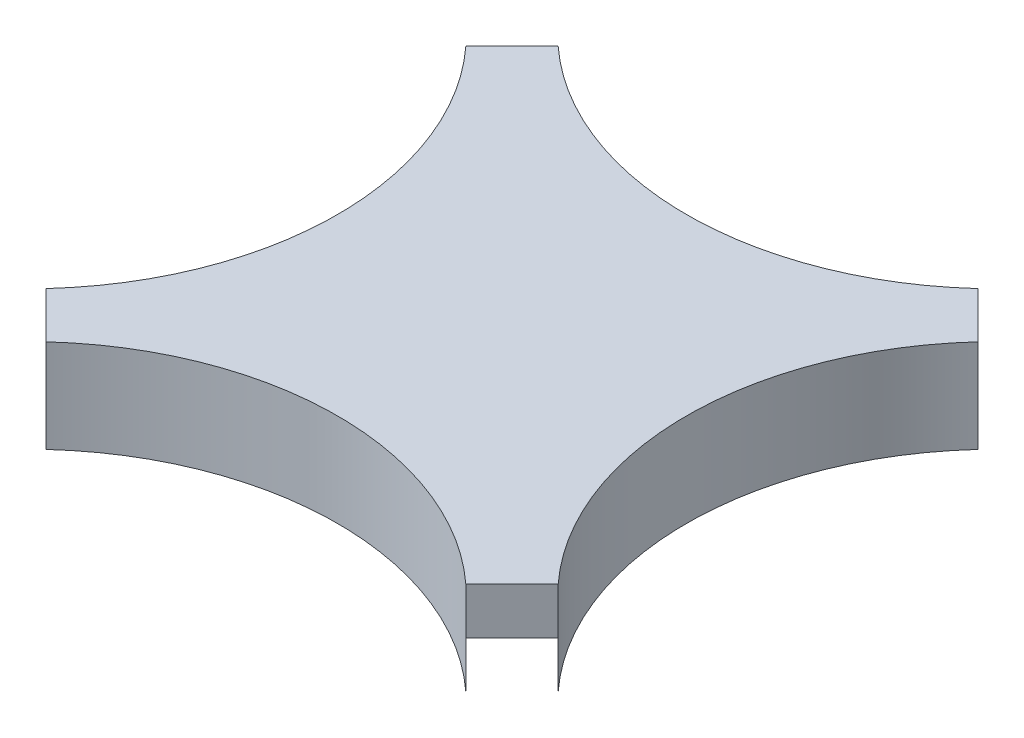
SolidWorks part; units mm, degrees
ref_plane "Front Plane" through (0, 0, 0) normal (0, 0, 1) x (1, 0, 0)
ref_plane "Top Plane" through (0, 0, 0) normal (0, 1, 0) x (1, 0, 0)
ref_plane "Right Plane" through (0, 0, 0) normal (1, 0, 0) x (0, 0, -1)
sketch "Sketch1" plane through (0, 0, 0) normal (0, 1, 0) x (1, 0, 0)
  line L0 (-8.2425, 6.7575) -> (-3.7644, 2.2794)
  line L1 (-7.5, 7.5) -> (7.5, 7.5) construction
  line L2 (-7.5, 7.5) -> (-7.5, -7.5) construction
  line L3 (-7.5, -7.5) -> (7.5, -7.5) construction
  line L4 (7.5, 7.5) -> (7.5, -7.5) construction
  line L5 (-7.5, 7.5) -> (7.5, -7.5) construction
  line L6 (-7.5, -7.5) -> (7.5, 7.5) construction
  line L7 (-6.7575, -8.2425) -> (-2.2794, -3.7644)
  line L8 (-6.7575, 8.2425) -> (-2.2794, 3.7644)
  line L9 (-8.2425, -6.7575) -> (-3.7644, -2.2794)
  line L10 (3.7644, 2.2794) -> (8.2425, 6.7575)
  line L11 (-6.7575, -8.2425) -> (8.2425, 6.7575) construction
  line L12 (3.7644, -2.2794) -> (8.2425, -6.7575)
  line L13 (-6.7575, 8.2425) -> (8.2425, -6.7575) construction
  line L14 (2.2794, -3.7644) -> (6.7575, -8.2425)
  line L15 (2.2794, 3.7644) -> (6.7575, 8.2425)
  line L16 (-8.2425, -6.7575) -> (6.7575, 8.2425) construction
  line L17 (-8.2425, 6.7575) -> (6.7575, -8.2425) construction
  line L18 (6.7575, 8.2425) -> (8.2425, 6.7575)
  line L19 (8.2425, -6.7575) -> (6.7575, -8.2425)
  line L20 (-6.7575, -8.2425) -> (-8.2425, -6.7575)
  line L21 (-8.2425, 6.7575) -> (-6.7575, 8.2425)
  arc A0 (3.7644, -2.2794) -> (3.7644, 2.2794) centre (6.4859, 0) cw
  arc A1 (-2.2794, -3.7644) -> (2.2794, -3.7644) centre (0, -6.4859) cw
  arc A2 (-3.7644, 2.2794) -> (-3.7644, -2.2794) centre (-6.4859, 0) cw
  arc A3 (2.2794, 3.7644) -> (-2.2794, 3.7644) centre (0, 6.4859) cw
  arc A4 (8.2425, -6.7575) -> (8.2425, 6.7575) centre (15.6137, 0) cw
  arc A5 (-6.7575, -8.2425) -> (6.7575, -8.2425) centre (0, -15.6137) cw
  arc A6 (-8.2425, 6.7575) -> (-8.2425, -6.7575) centre (-15.6137, 0) cw
  arc A7 (6.7575, 8.2425) -> (-6.7575, 8.2425) centre (0, 15.6137) cw
  point P0 (0, 0)
  dimension "D4" = 3.55
  dimension "D6" = 10
  dimension "D1" = 15
  dimension "D2" = 1.05
  dimension "D3" = 1.05
  dimension "D5" = 4
extrude "Boss-Extrude1" add sketch "Sketch1" along normal blind 1.5 and the other way blind 1.5 contours L15 A7 L8 A3 | L0 A6 L9 A2 | L7 A5 L14 A1 | L12 A4 L10 A0 region at (-4.9142, 0, 0) region at (0, 0, -4.9142) region at (0, 0, 4.9142) region at (4.9142, 0, 0)
extrude "Boss-Extrude2" add sketch "Sketch1<4>" along normal blind 1.5 contours L15 A3 L8 L21 L0 A2 L9 L20 L7 A1 L14 L19 L12 A0 L10 L18 region at (0, 0, 0)
sketch "Sketch1<4>" plane through (0, 0, 0) normal (0, 1, 0) x (1, 0, 0) same geometry as "Sketch1"
